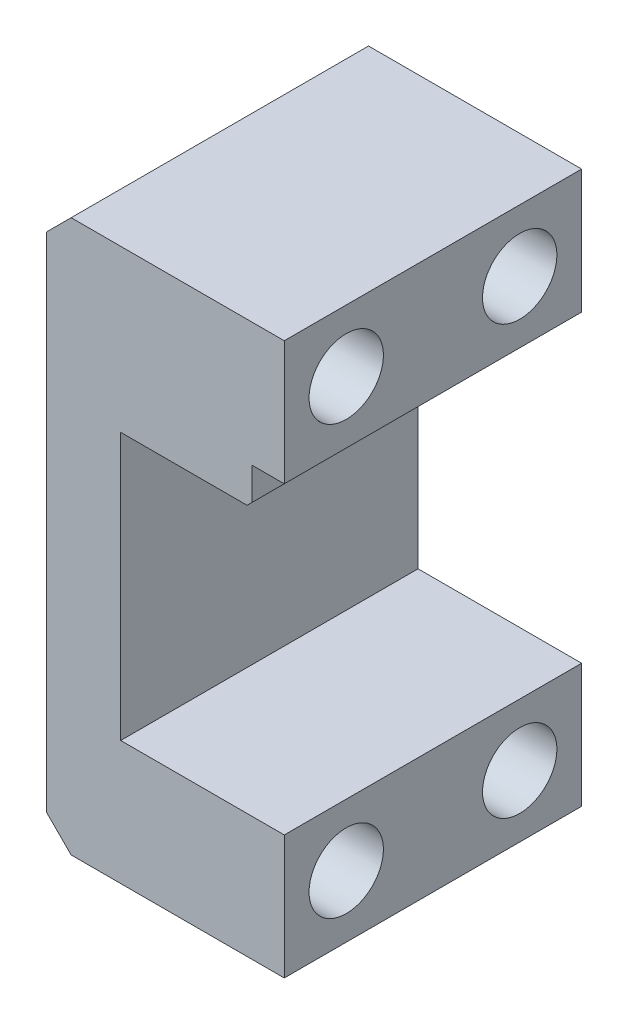
SolidWorks part; units mm, degrees
material "AISI 304"
ref_plane "前视基准面" through (0, 0, 0) normal (0, 0, 1) x (1, 0, 0)
ref_plane "上视基准面" through (0, 0, 0) normal (0, 1, 0) x (1, 0, 0)
ref_plane "右视基准面" through (0, 0, 0) normal (1, 0, 0) x (0, 0, -1)
sketch "草图1" plane through (0, 0, 0) normal (0, 0, 1) x (1, 0, 0)
  line L0 (0, 0) -> (0, 22.27)
  line L1 (0, 22.27) -> (9.6, 22.27)
  line L2 (9.6, 22.27) -> (9.6, 17.27)
  line L3 (9.6, 17.27) -> (8.3, 17.27)
  line L4 (8.3, 17.27) -> (8.3, 15.77)
  line L5 (8.3, 15.77) -> (3, 15.77)
  line L6 (3, 15.77) -> (3, 5)
  line L7 (3, 5) -> (9.6, 5)
  line L8 (9.6, 5) -> (9.6, 0)
  line L9 (9.6, 0) -> (0, 0)
  line L10 (9.6, 5) -> (9.6, 17.27) construction
  dimension "D1" = 5
  dimension "D2" = 10.77
  dimension "D3" = 3
  dimension "D4" = 1.3
  dimension "D5" = 6.6
  dimension "D6" = 1.5
  dimension "D7" = 5
extrude "凸台-拉伸1" add sketch "草图1" along normal blind 12
chamfer "倒角1" distance 0.2 angle 45 1 edges at (8.3, 15.77, 6)
sketch "草图2" plane through (0, 0, 0) normal (-1, 0, 0) x (0, 0, 1)
  line L0 (6, 22.27) -> (6, 0) construction
  line L1 (12, 22.27) -> (0, 22.27) construction
  line L2 (12, 0) -> (0, 0) construction
  line L3 (2.5, 19.77) -> (9.5, 19.77) construction
  line L4 (2.5, 2.5) -> (9.5, 2.5) construction
  line L5 (9.5, 2.5) -> (9.5, 19.77) construction
  line L6 (12, 22.27) -> (12, 0) construction
  circle A0 centre (9.5, 19.77) radius 1.5
  circle A1 centre (2.5, 19.77) radius 1.5
  circle A2 centre (2.5, 2.5) radius 1.5
  circle A3 centre (9.5, 2.5) radius 1.5
  point P9 (6, 19.77)
  point P12 (6, 2.5)
  dimension "D3" = 3
  dimension "D1" = 2.5
  dimension "D2" = 2.5
  dimension "D4" = 2.5
extrude "切除-拉伸1" cut sketch "草图2" against normal through all
chamfer "倒角2" distance 1 angle 45 2 edges at (0, 0, 6) (0, 22.27, 6)
